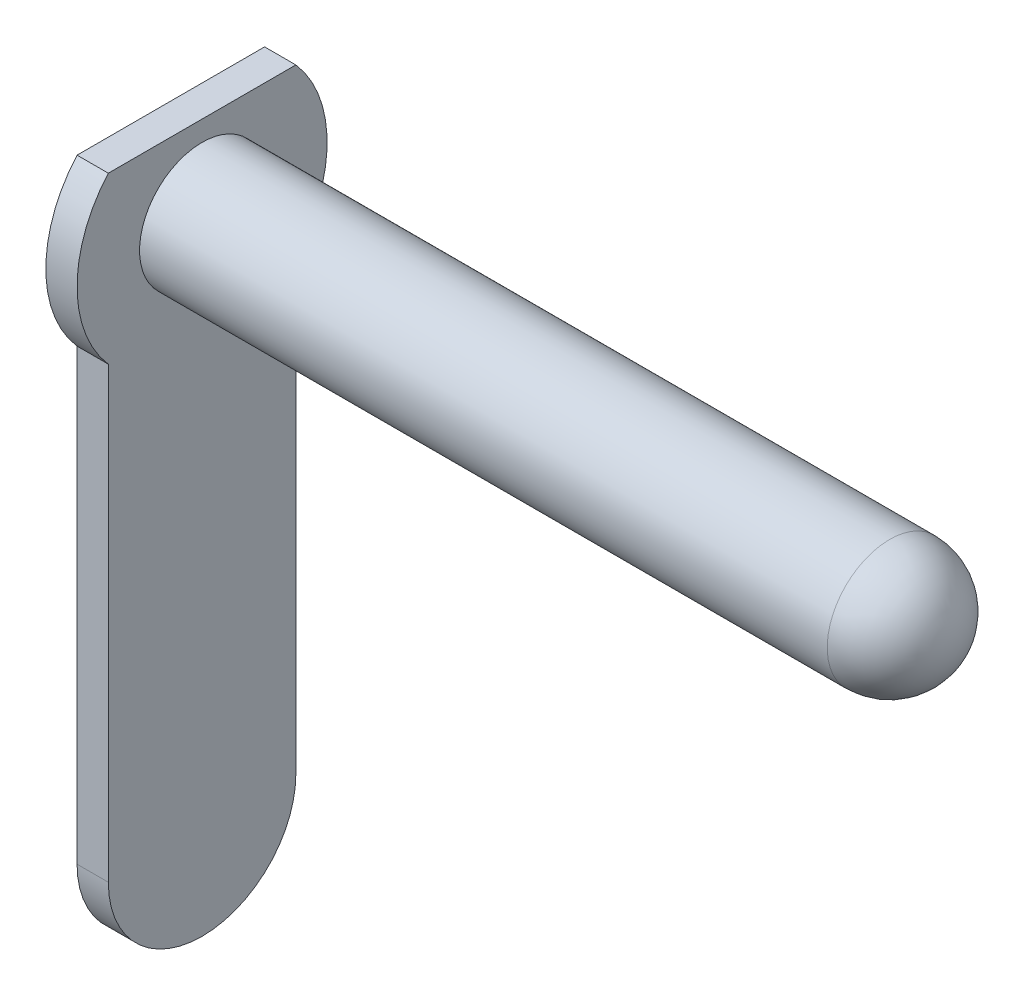
SolidWorks part; units mm, degrees
ref_plane "Front" through (0, 0, 0) normal (0, 0, 1) x (1, 0, 0)
ref_plane "Top" through (0, 0, 0) normal (0, 1, 0) x (1, 0, 0)
ref_plane "Right" through (0, 0, 0) normal (1, 0, 0) x (0, 0, -1)
sketch "Sketch1" plane through (0, 0, 0) normal (1, 0, 0) x (0, 0, -1)
  line L0 (0, 0) -> (0, 7.1771)
  line L1 (0, 7.1771) -> (3, 7.1771) construction
  line L2 (0, 0) -> (3, 0) construction
  line L3 (3, 7.1771) -> (3, 0)
  line L4 (1.5, 0) -> (1.5, 7.1771) construction
  line L5 (1.5, 7.1771) -> (1.5, 9.8229) construction
  line L6 (0, 0) -> (0, -1.5) construction
  line L7 (0, -1.5) -> (3, -1.5) construction
  line L8 (3, -1.5) -> (3, 0) construction
  line L9 (0, 7.1771) -> (0, 9.8229) construction
  line L10 (3, 7.1771) -> (3, 9.8229) construction
  line L11 (0, 9.8229) -> (3, 9.8229)
  arc A0 (0, 9.8229) -> (0, 7.1771) centre (1.5, 8.5) ccw
  arc A1 (0, 0) -> (3, 0) centre (1.5, 0) ccw
  arc A2 (3, 7.1771) -> (3, 9.8229) centre (1.5, 8.5) ccw
  dimension "D3" = 4
  dimension "D1" = 3
  dimension "D2" = 10
extrude "Boss-Extrude1" add sketch "Sketch1" along normal blind 0.5
sketch "Sketch2" plane through (0.5, 0, 0) normal (1, 0, 0) x (0, 0, -1)
  line L0 (1.5, -1.5) -> (1.5, 9.8229) construction
  line L1 (3, 9.8229) -> (0, 9.8229) construction
  line L2 (-0.5, 8.5) -> (3.5, 8.5) construction
  circle A0 centre (1.5, 8.5) radius 1
  arc A1 (0, 0) -> (3, 0) centre (1.5, 0) ccw construction
  arc A2 (0, 9.8229) -> (0, 7.1771) centre (1.5, 8.5) ccw construction
  arc A3 (3, 7.1771) -> (3, 9.8229) centre (1.5, 8.5) ccw construction
  dimension "D1" = 2
extrude "Boss-Extrude2" add sketch "Sketch2" along normal blind 12 and the other way blind 0.6
fillet "Fillet1" radius 1 1 edges at (12.5, 8.5, -2.5)
sketch "Sketch3" plane through (-0.1, 0, 0) normal (-1, 0, 0) x (0, 0, 1)
  circle A0 centre (-1.5, 8.5) radius 0.8
  dimension "D1" = 1.6
extrude "Cut-Extrude1" cut sketch "Sketch3" against normal blind 0.5
fillet "Fillet2" radius 0.1 3 edges at (-0.1, 8.5, -2.5) (-0.1, 8.5, -0.7) (0.4, 8.5, -0.7)
equation "\"`0.5\"=10"
